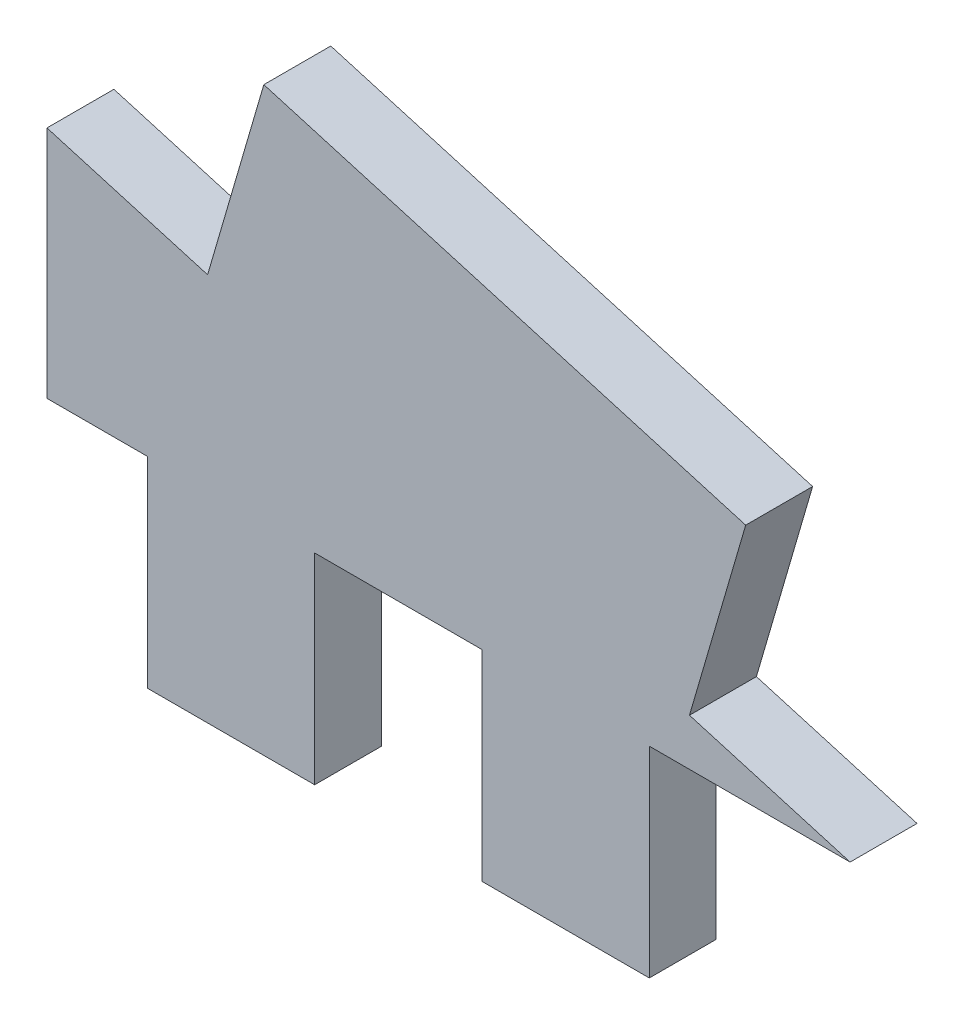
SolidWorks part; units mm, degrees
material "Thornel Mat VMA"
ref_plane "Ön Düzlem" through (0, 0, 0) normal (0, 0, 1) x (1, 0, 0)
ref_plane "Üst Düzlem" through (0, 0, 0) normal (0, 1, 0) x (1, 0, 0)
ref_plane "Sağ Düzlem" through (0, 0, 0) normal (1, 0, 0) x (0, 0, -1)
sketch "Çizim2" plane through (0, 0, 0) normal (0, 0, 1) x (1, 0, 0)
  line L0 (0, 0) -> (24, 0)
  line L1 (24, 0) -> (0, 7)
  line L2 (0, 7) -> (0, 0)
  line L3 (4.8, 5.6) -> (12, 3.5)
  line L4 (3, 0) -> (8, 0)
  line L5 (3, 0) -> (3, -6)
  line L6 (3, -6) -> (8, -6)
  line L7 (8, 0) -> (8, -6)
  line L8 (13, 0) -> (18, 0)
  line L9 (13, 0) -> (13, -6)
  line L10 (13, -6) -> (18, -6)
  line L11 (18, 0) -> (18, -6)
  line L12 (4.8, 5.6) -> (19.2, 1.4)
  line L13 (4.8, 5.6) -> (6.48, 11.36)
  line L14 (19.2, 1.4) -> (20.88, 7.16)
  line L15 (6.48, 11.36) -> (20.88, 7.16)
  dimension "D1" = 24
  dimension "D2" = 7
  dimension "D3" = 3
  dimension "D4" = 5
  dimension "D5" = 5
  dimension "D6" = 5
  dimension "D7" = 5
  dimension "D8" = 5
  dimension "D9" = 6
  dimension "D10" = 6
  dimension "D11" = 6
extrude "Yükseklik-Ekstrüzyon2" add sketch "Çizim2" along normal blind 2 contours L1 L2 L0 | L15 L13 L1 L14 | L7 L0 L5 L6 | L11 L0 L9 L10 region at (8, 2.3333, 0) region at (5.5, -3, 0) region at (12.84, 6.38, 0) region at (15.5, -3, 0)
